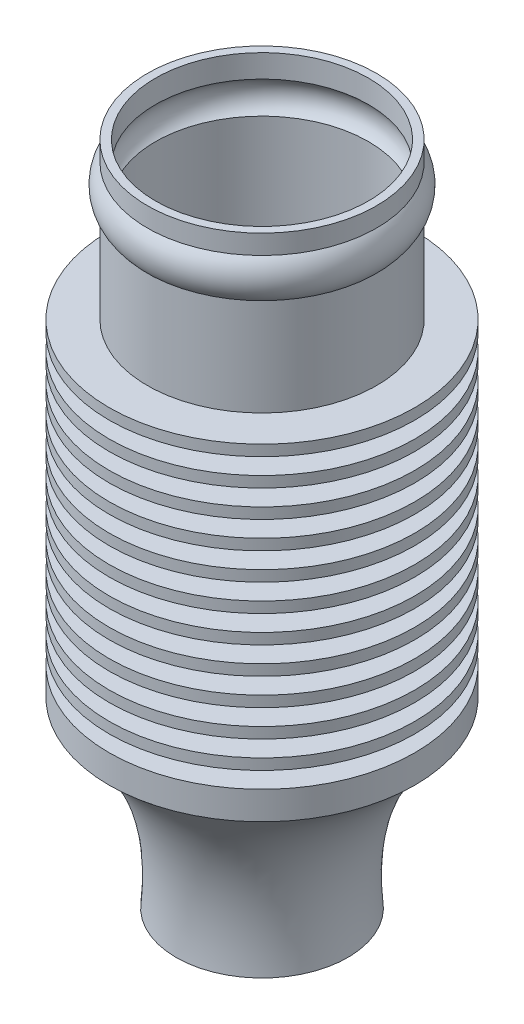
SolidWorks part; units mm, degrees
ref_plane "前视基准面" through (0, 0, 0) normal (0, 0, 1) x (1, 0, 0)
ref_plane "上视基准面" through (0, 0, 0) normal (0, 1, 0) x (1, 0, 0)
ref_plane "右视基准面" through (0, 0, 0) normal (1, 0, 0) x (0, 0, -1)
other "Configuration Table"
sketch "草图1" plane through (0, 0, 0) normal (0, 0, 1) x (1, 0, 0)
  line L0 (0, 0) -> (15.8018, 0)
  line L1 (28.1219, 33.6124) -> (0, 33.6124)
  line L2 (0, 33.6124) -> (0, 0)
  spline S0 degree 2 poles (15.8018, 0) (13.7828, 22.3812) (28.1219, 33.6124) knots 0 0 0 1 1 1
revolve "旋转1" add sketch "草图1" angle 360 about L2
sketch "草图3" plane through (0, 0, 0) normal (0, 0, 1) x (1, 0, 0)
  line L0 (28.1219, 33.6124) -> (0, 33.6124)
  line L1 (28.1219, 33.6124) -> (-28.1219, 33.6124) construction
  line L2 (0, 33.6124) -> (0, 96.7911)
  line L3 (0, 96.7911) -> (28.1219, 96.7911)
  line L4 (28.1219, 96.7911) -> (28.1219, 33.6124)
revolve "旋转2" add sketch "草图3" angle 360 about L2
sketch "草图4" plane through (0, 0, 0) normal (0, 0, 1) x (1, 0, 0)
  line L0 (21.0988, 96.7911) -> (37.9565, 96.7911)
  line L1 (28.1219, 96.7911) -> (-28.1219, 96.7911) construction
  line L2 (21.0988, 96.7911) -> (21.0988, 93.7911)
  line L3 (21.0988, 93.7911) -> (37.9565, 93.7911)
  line L4 (37.9565, 93.7911) -> (37.9565, 91.7911)
  line L5 (0, 0) -> (0, 123.6289) construction
  line L6 (21.0988, 88.7911) -> (37.9565, 88.7911)
  line L7 (21.0988, 91.7911) -> (21.0988, 88.7911)
  line L8 (21.0988, 91.7911) -> (37.9565, 91.7911)
  line L9 (37.9565, 88.7911) -> (37.9565, 86.7911)
  line L10 (21.0988, 83.7911) -> (37.9565, 83.7911)
  line L11 (21.0988, 86.7911) -> (21.0988, 83.7911)
  line L12 (21.0988, 86.7911) -> (37.9565, 86.7911)
  line L13 (37.9565, 83.7911) -> (37.9565, 81.7911)
  line L14 (21.0988, 78.7911) -> (37.9565, 78.7911)
  line L15 (21.0988, 81.7911) -> (21.0988, 78.7911)
  line L16 (21.0988, 81.7911) -> (37.9565, 81.7911)
  line L17 (37.9565, 78.7911) -> (37.9565, 76.7911)
  line L18 (21.0988, 73.7911) -> (37.9565, 73.7911)
  line L19 (21.0988, 76.7911) -> (21.0988, 73.7911)
  line L20 (21.0988, 76.7911) -> (37.9565, 76.7911)
  line L21 (37.9565, 73.7911) -> (37.9565, 71.7911)
  line L22 (21.0988, 68.7911) -> (37.9565, 68.7911)
  line L23 (21.0988, 71.7911) -> (21.0988, 68.7911)
  line L24 (21.0988, 71.7911) -> (37.9565, 71.7911)
  line L25 (37.9565, 68.7911) -> (37.9565, 66.7911)
  line L26 (21.0988, 63.7911) -> (37.9565, 63.7911)
  line L27 (21.0988, 66.7911) -> (21.0988, 63.7911)
  line L28 (21.0988, 66.7911) -> (37.9565, 66.7911)
  line L29 (37.9565, 63.7911) -> (37.9565, 61.7911)
  line L30 (21.0988, 58.7911) -> (37.9565, 58.7911)
  line L31 (21.0988, 61.7911) -> (21.0988, 58.7911)
  line L32 (21.0988, 61.7911) -> (37.9565, 61.7911)
  line L33 (37.9565, 58.7911) -> (37.9565, 56.7911)
  line L34 (21.0988, 53.7911) -> (37.9565, 53.7911)
  line L35 (21.0988, 56.7911) -> (21.0988, 53.7911)
  line L36 (21.0988, 56.7911) -> (37.9565, 56.7911)
  line L37 (37.9565, 53.7911) -> (37.9565, 51.7911)
  line L38 (21.0988, 48.7911) -> (37.9565, 48.7911)
  line L39 (21.0988, 51.7911) -> (21.0988, 48.7911)
  line L40 (21.0988, 51.7911) -> (37.9565, 51.7911)
  line L41 (37.9565, 48.7911) -> (37.9565, 46.7911)
  line L42 (21.0988, 43.7911) -> (37.9565, 43.7911)
  line L43 (21.0988, 46.7911) -> (21.0988, 43.7911)
  line L44 (21.0988, 46.7911) -> (37.9565, 46.7911)
  line L45 (37.9565, 43.7911) -> (37.9565, 41.7911)
  line L46 (21.0988, 38.7911) -> (37.9565, 38.7911)
  line L47 (21.0988, 41.7911) -> (21.0988, 38.7911)
  line L48 (21.0988, 41.7911) -> (37.9565, 41.7911)
  line L49 (37.9565, 38.7911) -> (37.9565, 36.7911)
  line L50 (37.9565, 36.7911) -> (74.6896, 36.7911)
  line L51 (74.6896, 36.7911) -> (74.6896, 104.6451)
  line L52 (74.6896, 104.6451) -> (37.9565, 104.6451)
  line L53 (37.9565, 104.6451) -> (37.9565, 96.7911)
  dimension "D1" = 3
  dimension "D2" = 2
  dimension "D3" = 12
revolve "切除-旋转1" cut sketch "草图4" angle 360 about L5
sketch "草图5" plane through (0, 0, 0) normal (0, 0, 1) x (1, 0, 0)
  line L0 (0, 96.7911) -> (0, 122.4581)
  line L1 (21.0988, 96.7911) -> (-21.0988, 96.7911) construction
  line L2 (21.0988, 122.4581) -> (21.0988, 118.8919)
  line L3 (21.0988, 96.7911) -> (0, 96.7911)
  line L4 (0, 122.4581) -> (21.0988, 122.4581)
  line L5 (21.0988, 111.6877) -> (21.0988, 96.7911)
  arc A0 (21.0988, 111.6877) -> (21.0988, 118.8919) centre (17.2416, 115.2898) ccw
revolve "旋转3" add sketch "草图5" angle 360 about L0
shell "抽壳2" thickness 1.5 removed face at (0, 122.4581, -21.0988)
